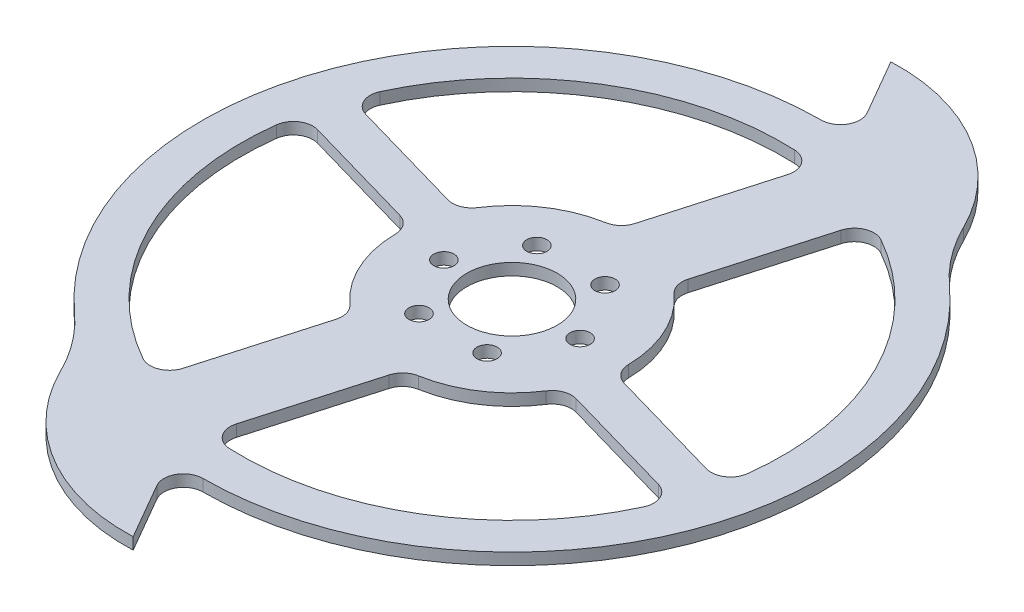
SolidWorks part; units mm, degrees
ref_plane "Front Plane" through (0, 0, 0) normal (0, 0, 1) x (1, 0, 0)
ref_plane "Top Plane" through (0, 0, 0) normal (0, 1, 0) x (1, 0, 0)
ref_plane "Right Plane" through (0, 0, 0) normal (1, 0, 0) x (0, 0, -1)
ref_axis "Axis1" through (0, -0.15, 0) along (0, 1, 0)
sketch "Sketch1" plane through (0, 0, 0) normal (0, 1, 0) x (1, 0, 0)
  line L1 (17.5, 0) -> (8.75, 15.1554) construction
  line L2 (8.75, 15.1554) -> (-8.75, 15.1554) construction
  line L3 (-8.75, 15.1554) -> (-17.5, 0) construction
  line L4 (-17.5, 0) -> (-8.75, -15.1554) construction
  line L5 (-8.75, -15.1554) -> (8.75, -15.1554) construction
  line L6 (8.75, -15.1554) -> (17.5, 0) construction
  circle A0 centre (0, 0) radius 15.1554 construction
  circle A1 centre (8.75, 15.1554) radius 2.6
  circle A2 centre (17.5, 0) radius 2.6
  circle A3 centre (8.75, -15.1554) radius 2.6
  circle A4 centre (-8.75, -15.1554) radius 2.6
  circle A5 centre (-17.5, 0) radius 2.6
  circle A6 centre (-8.75, 15.1554) radius 2.6
  circle A7 centre (0, 0) radius 11.6
  circle A8 centre (0, 0) radius 101.6 construction
  dimension "D1" = 5.2
  dimension "D2" = 23.2
  dimension "D3" = 203.2
  dimension "D4" = 35
sketch "Sketch2" plane through (0, 0, 0) normal (0, 1, 0) x (1, 0, 0)
  line L0 (0, -1000) -> (0, 49000) construction
  line L1 (-4.1612, 101.5147) -> (4.1612, 87.0998)
  line L2 (53.2301, 59.1837) -> (0, 0) construction
  line L3 (4.1612, 87.0998) -> (41.978, 74.0656) construction
  line L4 (-1000, 0) -> (49000, 0) construction
  line L5 (23.0696, 80.5827) -> (0, 0) construction
  line L6 (7.68, 63.1599) -> (-1.0629, 32.6209)
  line L7 (26.9076, 57.6554) -> (18.1647, 27.1163)
  line L8 (3.3086, 47.8904) -> (22.5362, 42.3858) construction
  line L9 (0, 0) -> (-66.912, 19.1559) construction
  line L10 (-59.9803, 22.3723) -> (-30.3676, 13.8946)
  line L11 (-62.7326, 12.7585) -> (-33.1198, 4.2809)
  line L12 (-45.1739, 18.1335) -> (-47.9262, 8.5197) construction
  circle A0 centre (0, 0) radius 101.6 construction
  arc A1 (-4.1612, 101.5147) -> (41.978, 74.0656) centre (-2.1478, 52.3969) cw
  arc A2 (41.978, 74.0656) -> (53.2301, 59.1837) centre (86.1038, 95.7342) ccw
  circle A3 centre (0, 0) radius 79.6 construction
  arc A4 (4.1612, 87.0998) -> (-0.1589, 79.5998) centre (-0.1689, 84.5998) cw
  circle A5 centre (0, 0) radius 29.5 construction
  circle A6 centre (0, 0) radius 69.6 construction
  arc A7 (18.1647, 27.1163) -> (19.6424, 22.0097) centre (22.9716, 25.7401) ccw
  arc A8 (26.9076, 57.6554) -> (34.1692, 60.6352) centre (31.7145, 56.2792) cw
  arc A9 (-1.0629, 32.6209) -> (-5.0191, 29.0699) centre (-5.8698, 33.997) cw
  arc A10 (7.68, 63.1599) -> (3.0955, 69.5311) centre (2.8731, 64.5361) ccw
  arc A11 (-0.1589, 79.5998) -> (53.2301, 59.1837) centre (0, 0) ccw
  arc A12 (-30.3676, 13.8946) -> (-24.7898, 15.9912) centre (-28.9914, 18.7015) ccw
  arc A13 (-33.1198, 4.2809) -> (-29.4966, -0.4498) centre (-34.496, -0.526) cw
  arc A14 (-62.7326, 12.7585) -> (-69.0707, 8.5671) centre (-64.1087, 7.9516) ccw
  arc A15 (-59.9803, 22.3723) -> (-63.1401, 29.2829) centre (-58.6042, 27.1792) cw
  arc A16 (3.0955, 69.5311) -> (-63.1401, 29.2829) centre (0, 0) ccw
  arc A17 (-69.0707, 8.5671) -> (34.1692, 60.6352) centre (0, 0) ccw
  arc A18 (-5.0191, 29.0699) -> (-24.7898, 15.9912) centre (0, 0) ccw
  arc A19 (19.6424, 22.0097) -> (-29.4966, -0.4498) centre (0, 0) cw
  point P7 (0, 94.3073)
  point P16 (-79.6, 0)
  point P17 (-101.6, 0)
  point P21 (29.5, 0)
  point P25 (-69.6, 0)
  point P34 (12.9224, 45.1381)
  point P49 (-46.5501, 13.3266)
  dimension "D3" = 5
  dimension "D8" = 5
  dimension "D1" = 30
  dimension "D2" = 22
  dimension "D4" = 40
  dimension "D5" = 12
  dimension "D6" = 10
  dimension "D7" = 20
  dimension "D9" = 10
extrude "Boss-Extrude1" add sketch "Sketch2" along normal blind 3.02
pattern_circular "CirPattern1" count 2 over 360 about axis through (0, -0.15, 0) along (0, 1, 0) of bodies 101
combine bodies "Combine1" bodies to combine 101 102
extrude "Cut-Extrude2" cut sketch "Sketch1" along normal through all
